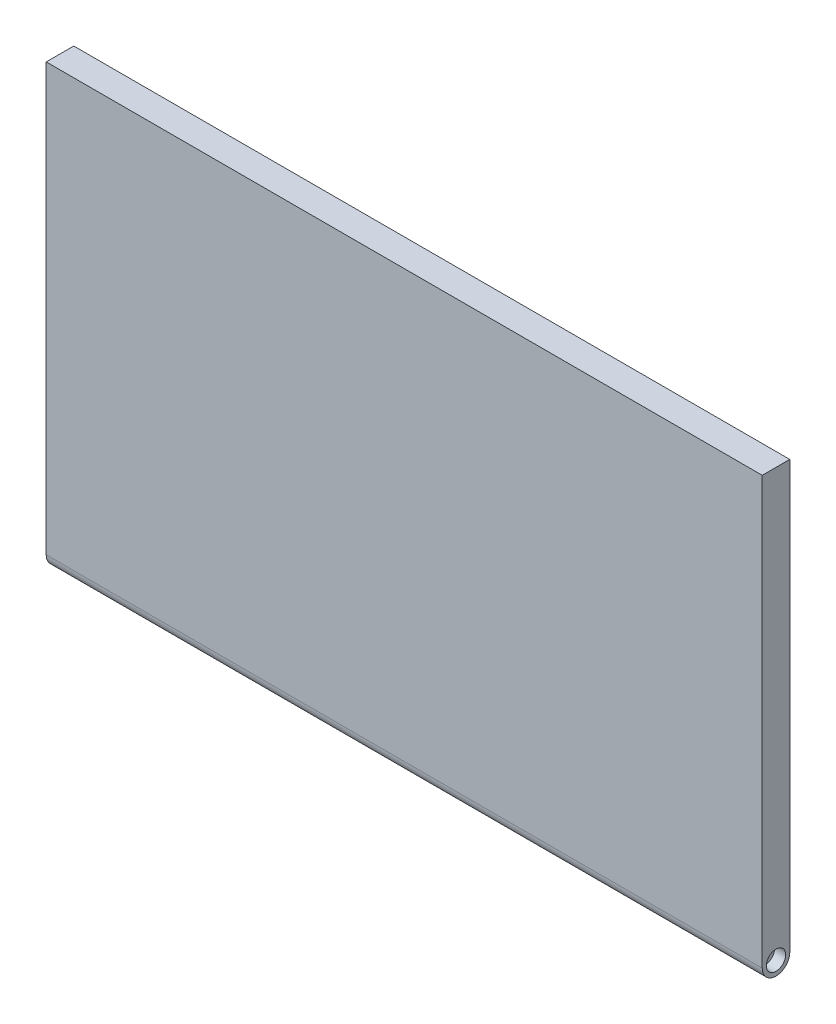
SolidWorks part; units mm, degrees
ref_plane "Front Plane" through (0, 0, 0) normal (0, 0, 1) x (1, 0, 0)
ref_plane "Top Plane" through (0, 0, 0) normal (0, 1, 0) x (1, 0, 0)
ref_plane "Right Plane" through (0, 0, 0) normal (1, 0, 0) x (0, 0, -1)
sketch "Sketch1" plane through (0, 0, 0) normal (0, 0, 1) x (1, 0, 0)
  line L1 (-65, -40) -> (65, -40)
  line L2 (-65, -40) -> (-65, 40)
  line L3 (-65, 40) -> (65, 40)
  line L4 (65, -40) -> (65, 40)
  line L5 (-65, -40) -> (65, 40) construction
  line L6 (-65, 40) -> (65, -40) construction
  point P0 (0, 0)
  dimension "D1" = 130
  dimension "D2" = 80
extrude "Boss-Extrude1" add sketch "Sketch1" along normal blind 5
fillet "Fillet1" radius 2.5 2 edges at (0, -40, 0) (0, -40, 5)
sketch "Sketch2" plane through (65, 0, 0) normal (1, 0, 0) x (0, 0, -1)
  circle A0 centre (-2.5, -37.5) radius 1.75
  dimension "D1" = 3.5
extrude "Cut-Extrude1" cut sketch "Sketch2" against normal blind 2
